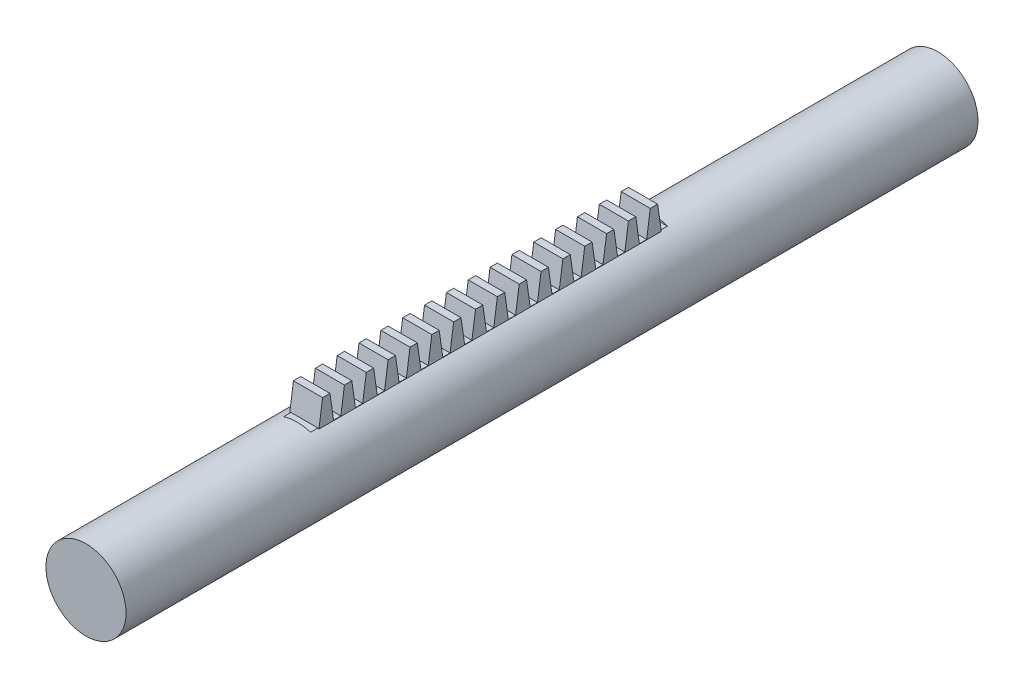
SolidWorks part; units mm, degrees
ref_plane "Front Plane" through (0, 0, 0) normal (0, 0, 1) x (1, 0, 0)
ref_plane "Top Plane" through (0, 0, 0) normal (0, 1, 0) x (1, 0, 0)
ref_plane "Right Plane" through (0, 0, 0) normal (1, 0, 0) x (0, 0, -1)
sketch "Sketch1" plane through (0, 0, 0) normal (0, 0, 1) x (1, 0, 0)
  line L0 (0, 11.9824) -> (0, -9.1713)
  line L1 (-2, 8.6235) -> (-2, 5.1235)
  line L2 (2, 8.6235) -> (2, 5.1235)
  line L3 (-2, 8.6235) -> (2, 8.6235)
  circle A0 centre (0, 0) radius 4.5
  circle A1 centre (0, 0) radius 5.5
  dimension "D1" = 9
  dimension "D2" = 11
  dimension "D3" = 2
  dimension "D4" = 3.5
extrude "Boss-Extrude3" add sketch "Sketch1" along normal blind 117 contours A1 L0 A0 | L0 A1 A0 | L0 A0 | L0 A0 region at (0.9948, 5.2842, 0) region at (-0.123, 5, 0) region at (1.9099, 0, 0) region at (-1.9099, 0, 0)
extrude "Cut-Extrude4" cut sketch "Sketch1<3>" along normal blind 115 contours L0 A0 | L0 A0 region at (1.9099, 0, 0) region at (-1.9099, 0, 0)
sketch "Sketch1<3>" plane through (0, 0, 0) normal (0, 0, 1) x (1, 0, 0) same geometry as "Sketch1"
extrude "Boss-Extrude4" add sketch "Sketch1<4>" along normal blind 87 contours A1 L0 L3 L1 | A1 L2 L3 L0 region at (1.0192, 6.9979, 0) region at (-1.0192, 6.9979, 0)
sketch "Sketch1<4>" plane through (0, 0, 0) normal (0, 0, 1) x (1, 0, 0) same geometry as "Sketch1"
extrude "Cut-Extrude5" cut sketch "Sketch1<5>" along normal blind 40 contours A1 L2 L3 L0 | A1 L0 L3 L1 region at (1.0192, 6.9979, 0) region at (-1.0192, 6.9979, 0)
sketch "Sketch1<5>" plane through (0, 0, 0) normal (0, 0, 1) x (1, 0, 0) same geometry as "Sketch1"
ref_plane "Plane2" through (2, 0, 0) normal (1, 0, 0) x (0, 0, -1)
sketch "Sketch11" plane through (2, 0, 0) normal (1, 0, 0) x (0, 0, -1)
  line L0 (-63.5, 16.0448) -> (-63.5, -8.6455) construction
  line L1 (-63.5, 8.6645) -> (-62.5, 8.6645)
  line L2 (-63.5, 5.1796) -> (-63, 5.1796)
  line L3 (-62.5, 8.6645) -> (-63, 5.1796)
  line L4 (-63.5, 8.6645) -> (-64.5, 8.6645)
  line L5 (-63.5, 5.1796) -> (-64, 5.1796)
  line L6 (-64.5, 8.6645) -> (-64, 5.1796)
  line L7 (-61.5, 8.6645) -> (-61, 5.1796)
  line L8 (-59.5, 8.6645) -> (-60, 5.1796)
  line L9 (-60.5, 8.6645) -> (-59.5, 8.6645)
  line L10 (-60.5, 8.6645) -> (-61.5, 8.6645)
  line L11 (-60.5, 5.1796) -> (-61, 5.1796)
  line L12 (-60.5, 5.1796) -> (-60, 5.1796)
  line L13 (-58.5, 8.6645) -> (-58, 5.1796)
  line L14 (-56.5, 8.6645) -> (-57, 5.1796)
  line L15 (-57.5, 8.6645) -> (-56.5, 8.6645)
  line L16 (-57.5, 8.6645) -> (-58.5, 8.6645)
  line L17 (-57.5, 5.1796) -> (-58, 5.1796)
  line L18 (-57.5, 5.1796) -> (-57, 5.1796)
  line L19 (-55.5, 8.6645) -> (-55, 5.1796)
  line L20 (-53.5, 8.6645) -> (-54, 5.1796)
  line L21 (-54.5, 8.6645) -> (-53.5, 8.6645)
  line L22 (-54.5, 8.6645) -> (-55.5, 8.6645)
  line L23 (-54.5, 5.1796) -> (-55, 5.1796)
  line L24 (-54.5, 5.1796) -> (-54, 5.1796)
  line L25 (-52.5, 8.6645) -> (-52, 5.1796)
  line L26 (-50.5, 8.6645) -> (-51, 5.1796)
  line L27 (-51.5, 8.6645) -> (-50.5, 8.6645)
  line L28 (-51.5, 8.6645) -> (-52.5, 8.6645)
  line L29 (-51.5, 5.1796) -> (-52, 5.1796)
  line L30 (-51.5, 5.1796) -> (-51, 5.1796)
  line L31 (-49.5, 8.6645) -> (-49, 5.1796)
  line L32 (-47.5, 8.6645) -> (-48, 5.1796)
  line L33 (-48.5, 8.6645) -> (-47.5, 8.6645)
  line L34 (-48.5, 8.6645) -> (-49.5, 8.6645)
  line L35 (-48.5, 5.1796) -> (-49, 5.1796)
  line L36 (-48.5, 5.1796) -> (-48, 5.1796)
  line L37 (-46.5, 8.6645) -> (-46, 5.1796)
  line L38 (-44.5, 8.6645) -> (-45, 5.1796)
  line L39 (-45.5, 8.6645) -> (-44.5, 8.6645)
  line L40 (-45.5, 8.6645) -> (-46.5, 8.6645)
  line L41 (-45.5, 5.1796) -> (-46, 5.1796)
  line L42 (-45.5, 5.1796) -> (-45, 5.1796)
  line L43 (-43.5, 8.6645) -> (-43, 5.1796)
  line L44 (-41.5, 8.6645) -> (-42, 5.1796)
  line L45 (-42.5, 8.6645) -> (-41.5, 8.6645)
  line L46 (-42.5, 8.6645) -> (-43.5, 8.6645)
  line L47 (-42.5, 5.1796) -> (-43, 5.1796)
  line L48 (-42.5, 5.1796) -> (-42, 5.1796)
  line L49 (-40.5, 8.6645) -> (-40, 5.1796)
  line L50 (-38.5, 8.6645) -> (-39, 5.1796)
  line L51 (-39.5, 8.6645) -> (-38.5, 8.6645)
  line L52 (-39.5, 8.6645) -> (-40.5, 8.6645)
  line L53 (-39.5, 5.1796) -> (-40, 5.1796)
  line L54 (-39.5, 5.1796) -> (-39, 5.1796)
  line L55 (-67.5, 8.6645) -> (-67, 5.1796)
  line L56 (-65.5, 8.6645) -> (-66, 5.1796)
  line L57 (-66.5, 8.6645) -> (-65.5, 8.6645)
  line L58 (-66.5, 8.6645) -> (-67.5, 8.6645)
  line L59 (-66.5, 5.1796) -> (-67, 5.1796)
  line L60 (-66.5, 5.1796) -> (-66, 5.1796)
  line L61 (-70.5, 8.6645) -> (-70, 5.1796)
  line L62 (-68.5, 8.6645) -> (-69, 5.1796)
  line L63 (-69.5, 8.6645) -> (-68.5, 8.6645)
  line L64 (-69.5, 8.6645) -> (-70.5, 8.6645)
  line L65 (-69.5, 5.1796) -> (-70, 5.1796)
  line L66 (-69.5, 5.1796) -> (-69, 5.1796)
  line L67 (-73.5, 8.6645) -> (-73, 5.1796)
  line L68 (-71.5, 8.6645) -> (-72, 5.1796)
  line L69 (-72.5, 8.6645) -> (-71.5, 8.6645)
  line L70 (-72.5, 8.6645) -> (-73.5, 8.6645)
  line L71 (-72.5, 5.1796) -> (-73, 5.1796)
  line L72 (-72.5, 5.1796) -> (-72, 5.1796)
  line L73 (-76.5, 8.6645) -> (-76, 5.1796)
  line L74 (-74.5, 8.6645) -> (-75, 5.1796)
  line L75 (-75.5, 8.6645) -> (-74.5, 8.6645)
  line L76 (-75.5, 8.6645) -> (-76.5, 8.6645)
  line L77 (-75.5, 5.1796) -> (-76, 5.1796)
  line L78 (-75.5, 5.1796) -> (-75, 5.1796)
  line L79 (-79.5, 8.6645) -> (-79, 5.1796)
  line L80 (-77.5, 8.6645) -> (-78, 5.1796)
  line L81 (-78.5, 8.6645) -> (-77.5, 8.6645)
  line L82 (-78.5, 8.6645) -> (-79.5, 8.6645)
  line L83 (-78.5, 5.1796) -> (-79, 5.1796)
  line L84 (-78.5, 5.1796) -> (-78, 5.1796)
  line L85 (-82.5, 8.6645) -> (-82, 5.1796)
  line L86 (-80.5, 8.6645) -> (-81, 5.1796)
  line L87 (-81.5, 8.6645) -> (-80.5, 8.6645)
  line L88 (-81.5, 8.6645) -> (-82.5, 8.6645)
  line L89 (-81.5, 5.1796) -> (-82, 5.1796)
  line L90 (-81.5, 5.1796) -> (-81, 5.1796)
  line L91 (-85.5, 8.6645) -> (-85, 5.1796)
  line L92 (-83.5, 8.6645) -> (-84, 5.1796)
  line L93 (-84.5, 8.6645) -> (-83.5, 8.6645)
  line L94 (-84.5, 8.6645) -> (-85.5, 8.6645)
  line L95 (-84.5, 5.1796) -> (-85, 5.1796)
  line L96 (-84.5, 5.1796) -> (-84, 5.1796)
  line L97 (-88.5, 8.6645) -> (-88, 5.1796)
  line L98 (-86.5, 8.6645) -> (-87, 5.1796)
  line L99 (-87.5, 8.6645) -> (-86.5, 8.6645)
  line L100 (-87.5, 8.6645) -> (-88.5, 8.6645)
  line L101 (-87.5, 5.1796) -> (-88, 5.1796)
  line L102 (-87.5, 5.1796) -> (-87, 5.1796)
extrude "Cut-Extrude6" cut sketch "Sketch11" against normal blind 4 contours L95 L96 L92 L93 L94 L91 | L71 L72 L68 L69 L70 L67 | L29 L30 L26 L27 L28 L25 | L41 L42 L38 L39 L40 L37 | L53 L54 L50 L51 L52 L49 | L86 L90 L89 L85 L88 L87 | L79 L83 L84 L80 L81 L82 | L74 L78 L77 L73 L76 L75 | L61 L65 L66 L62 L63 L64 | L56 L60 L59 L55 L58 L57 | L3 L2 L5 L6 L4 L1 | L7 L11 L12 L8 L9 L10 | L13 L17 L18 L14 L15 L16 | L20 L24 L23 L19 L22 L21 | L31 L35 L36 L32 L33 L34 | L44 L48 L47 L43 L46 L45 | L98 L102 L101 L97 L100 L99 region at (2, 7.1157, 51.5) region at (2, 7.1157, 45.5) region at (2, 7.1157, 39.5) region at (2, 7.1157, 72.5) region at (2, 7.1157, 84.5)
